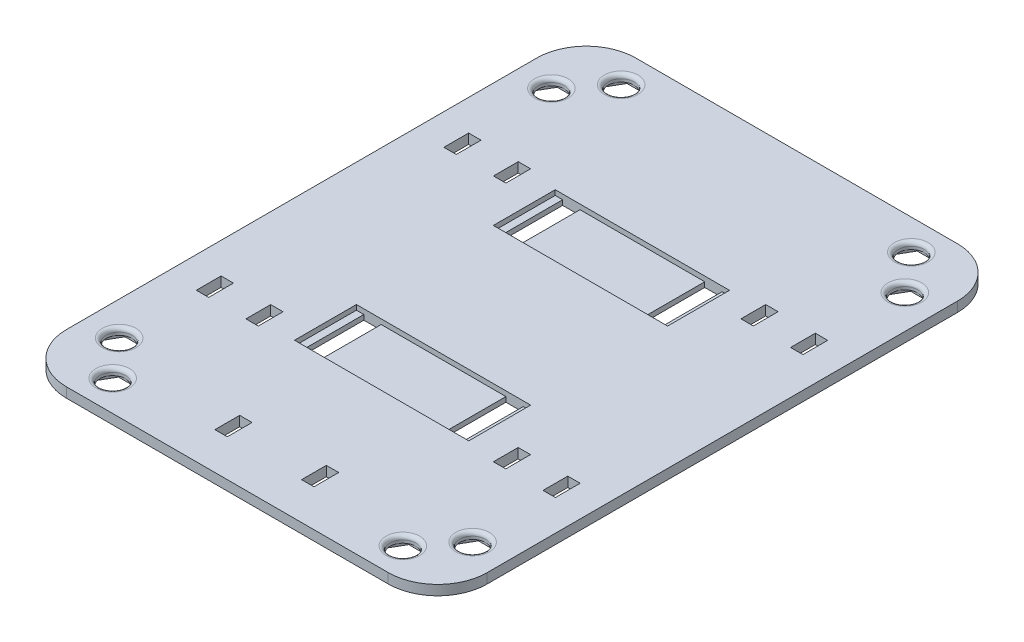
SolidWorks part; units mm, degrees
material "3-D Printed ABS"
ref_plane "Front Plane" through (0, 0, 0) normal (0, 0, 1) x (1, 0, 0)
ref_plane "Top Plane" through (0, 0, 0) normal (0, 1, 0) x (1, 0, 0)
ref_plane "Right Plane" through (0, 0, 0) normal (1, 0, 0) x (0, 0, -1)
sketch "Sketch1" plane through (0, 0, 0) normal (0, 1, 0) x (1, 0, 0)
  line L1 (-53.975, -73.025) -> (53.975, -73.025)
  line L2 (-53.975, -73.025) -> (-53.975, 73.025)
  line L3 (-53.975, 73.025) -> (53.975, 73.025)
  line L4 (53.975, -73.025) -> (53.975, 73.025)
  line L5 (-53.975, -73.025) -> (53.975, 73.025) construction
  line L6 (-53.975, 73.025) -> (53.975, -73.025) construction
  point P0 (0, 0)
  dimension "D1" = 107.95
  dimension "PlateY" = 146.05
extrude "Boss-Extrude1" add sketch "Sketch1" against normal blind 2.54
sketch "Sketch2" plane through (0, 0, 0) normal (0, 1, 0) x (1, 0, 0)
  line L0 (0, 0) -> (152.4, 0) construction
  line L1 (0, 0) -> (0, 152.4) construction
  line L4 (0, 0) -> (-53.975, 73.025) construction
  line L5 (0, 0) -> (-152.4, 0) construction
  line L6 (0, 0) -> (-152.4, 152.4) construction
  line L7 (-53.975, 73.025) -> (-53.975, -73.025) construction
  line L8 (53.975, 73.025) -> (-53.975, 73.025) construction
  line L9 (-152.4, 152.4) -> (-41.275, 60.325) construction
  line L10 (-41.275, 60.325) -> (0, 26.1257) construction
  line L11 (-30.7521, 73.025) -> (-53.975, 44.9974) construction
  circle A0 centre (-37.2189, 65.2108) radius 3.302
  circle A1 centre (45.3264, 55.4354) radius 3.302
  circle A2 centre (37.2189, 65.2108) radius 3.302
  circle A3 centre (-45.3264, -55.4354) radius 3.302
  circle A4 centre (-45.3264, 55.4354) radius 3.302
  circle A5 centre (-37.2189, -65.2108) radius 3.302
  circle A6 centre (37.2189, -65.2108) radius 3.302
  circle A7 centre (45.3264, -55.4354) radius 3.302
  point P12 (-41.275, 60.325)
  point P15 (-37.2189, 65.2108)
  dimension "D1" = 6.604
  dimension "D3" = 12.7
  dimension "D8" = 6.604
  dimension "D2" = 12.7
  dimension "D4" = 152.4
  dimension "D5" = 152.4
  dimension "D6" = 152.4
  dimension "D7" = 6.35
  dimension "D9" = 6.35
extrude "Cut-Extrude1" cut sketch "Sketch2" against normal through all
sketch "Sketch3" plane through (0, 0, 0) normal (0, 1, 0) x (1, 0, 0)
  line L0 (-53.975, 0) -> (53.975, 0) construction
  line L1 (-20.445, 33.4374) -> (-16, 33.4374)
  line L2 (-20.445, 33.4374) -> (-20.445, 17.5624)
  line L3 (-20.445, 17.5624) -> (-16, 17.5624)
  line L4 (-16, 33.4374) -> (-16, 17.5624)
  line L5 (16, 33.4374) -> (16, 17.5624)
  line L6 (20.445, 17.5624) -> (16, 17.5624)
  line L7 (20.445, 33.4374) -> (20.445, 17.5624)
  line L8 (20.445, 33.4374) -> (16, 33.4374)
  line L9 (-53.975, 73.025) -> (-53.975, -73.025) construction
  line L10 (53.975, -73.025) -> (53.975, 73.025) construction
  line L11 (0, -25.4999) -> (0, 79.6704) construction
  line L12 (0, 25.4999) -> (0, -79.6704) construction
  line L13 (20.445, -33.4374) -> (16, -33.4374)
  line L14 (20.445, -33.4374) -> (20.445, -17.5624)
  line L15 (20.445, -17.5624) -> (16, -17.5624)
  line L16 (16, -33.4374) -> (16, -17.5624)
  line L17 (-16, -33.4374) -> (-16, -17.5624)
  line L18 (-20.445, -17.5624) -> (-16, -17.5624)
  line L19 (-20.445, -33.4374) -> (-20.445, -17.5624)
  line L20 (-20.445, -33.4374) -> (-16, -33.4374)
  line L21 (-20.445, 25.4999) -> (-32.442, 25.4999) construction
  line L22 (-53.975, -73.025) -> (53.975, -73.025) construction
  point P31 (0, -73.025)
  point P32 (-53.975, 0)
  dimension "D1" = 15.875
  dimension "D2" = 4.445
  dimension "D3" = 16
  dimension "D4" = 25.4999
  dimension "D5" = 25.4999
extrude "Cut-Extrude2" cut sketch "Sketch3" against normal through all
fillet "Fillet1" radius 12.7 4 edges at (53.975, -1.27, -73.025) (53.975, -1.27, 73.025) (-53.975, -1.27, 73.025) (-53.975, -1.27, -73.025)
sketch "Sketch4" plane through (0, 0, 0) normal (0, 1, 0) x (1, 0, 0)
  line L0 (0, 0) -> (80.9727, -80.9727) construction
  line L1 (0, 0) -> (-80.9727, -80.9727) construction
  line L2 (69.1118, -51.1513) -> (28.7006, -10.7401)
  line L3 (28.7006, -10.7401) -> (10.7401, -28.7006)
  line L4 (10.7401, -28.7006) -> (51.1513, -69.1118)
  line L5 (51.1513, -69.1118) -> (69.1118, -51.1513)
  line L6 (0, 0) -> (0, -118.7381) construction
  line L7 (0, 0) -> (-98.4177, 0) construction
  line L8 (-51.1513, -69.1118) -> (-69.1118, -51.1513)
  line L9 (-69.1118, -51.1513) -> (-28.7006, -10.7401)
  line L10 (-28.7006, -10.7401) -> (-10.7401, -28.7006)
  line L11 (-10.7401, -28.7006) -> (-51.1513, -69.1118)
  line L12 (-69.1118, 51.1513) -> (-28.7006, 10.7401)
  line L13 (-51.1513, 69.1118) -> (-69.1118, 51.1513)
  line L14 (-10.7401, 28.7006) -> (-51.1513, 69.1118)
  line L15 (-28.7006, 10.7401) -> (-10.7401, 28.7006)
  line L16 (51.1513, 69.1118) -> (69.1118, 51.1513)
  line L17 (69.1118, 51.1513) -> (28.7006, 10.7401)
  line L18 (28.7006, 10.7401) -> (10.7401, 28.7006)
  line L19 (10.7401, 28.7006) -> (51.1513, 69.1118)
  point P6 (19.7204, -19.7204)
  dimension "D1" = 25.4
  dimension "D2" = 57.15
  dimension "D3" = 45
extrude "Cut-Extrude3" [suppressed] cut sketch "Sketch4" against normal blind 1.5875
sketch "Sketch6" [suppressed] plane through (0, 0, 0) normal (0, 1, 0) x (1, 0, 0)
  line L0 (46.3377, -44.1074) -> (34.6634, -32.4331) construction
  line L1 (0, 0) -> (0, -117.7376) construction
  line L2 (0, 0) -> (-151.7285, 0) construction
  line L4 (28.1601, -10.1996) -> (10.1996, -28.1601) construction
  line L5 (50.6107, -68.5712) -> (68.5712, -50.6107) construction
  text T0 "ESC" font "Century Gothic" height in points 22
  dimension "D1" = 45
  dimension "D2" = 20.32
  dimension "D3" = 20.32
extrude "Cut-Extrude5" [suppressed] cut sketch "Sketch6" against normal blind 3.175
sketch "Sketch5" plane through (0, 0, 0) normal (0, 1, 0) x (1, 0, 0)
  line L0 (41.275, 73.025) -> (-41.275, 73.025) construction
  line L1 (14.2875, 15.875) -> (-14.2875, 15.875)
  line L2 (14.2875, 15.875) -> (14.2875, 66.675)
  line L3 (14.2875, 66.675) -> (-14.2875, 66.675)
  line L4 (-14.2875, 15.875) -> (-14.2875, 66.675)
  point P4 (0, 15.875)
  dimension "D1" = 50.8
  dimension "D2" = 28.575
  dimension "D3" = 6.35
extrude "Cut-Extrude4" [suppressed] cut sketch "Sketch5" against normal blind 1.5875
ref_axis "Axis1" through (0, 0.3175, 0) along (0, -1, 0)
pattern_circular "CirPattern1" [suppressed] count 4 over 360 about axis through (0, 0.3175, 0) along (0, -1, 0) of bodies 105
sketch "Sketch7" plane through (0, 0, 0) normal (0, 1, 0) x (1, 0, 0)
  line L0 (0, 0) -> (0, -54.962) construction
  line L1 (63.4018, -13.3522) -> (38.0018, -13.3522)
  line L2 (63.4018, -13.3522) -> (63.4018, 43.7978)
  line L3 (63.4018, 43.7978) -> (38.0018, 43.7978)
  line L4 (38.0018, -13.3522) -> (38.0018, 43.7978)
  line L5 (-38.0018, -13.3522) -> (-38.0018, 43.7978)
  line L6 (-63.4018, 43.7978) -> (-38.0018, 43.7978)
  line L7 (-63.4018, -13.3522) -> (-63.4018, 43.7978)
  line L8 (-63.4018, -13.3522) -> (-38.0018, -13.3522)
  line L9 (-41.275, -73.025) -> (41.275, -73.025) construction
  line L10 (38.5677, -40.64) -> (-18.5823, -40.64)
  line L11 (38.5677, -40.64) -> (38.5677, -66.04)
  line L12 (38.5677, -66.04) -> (-18.5823, -66.04)
  line L13 (-18.5823, -40.64) -> (-18.5823, -66.04)
  line L14 (38.5677, -40.64) -> (-18.5823, -66.04) construction
  line L15 (38.5677, -66.04) -> (-18.5823, -40.64) construction
  line L16 (19.844, -36.1003) -> (-37.306, -36.1003)
  line L17 (19.844, -36.1003) -> (19.844, -61.5003)
  line L18 (19.844, -61.5003) -> (-37.306, -61.5003)
  line L19 (-37.306, -36.1003) -> (-37.306, -61.5003)
  line L20 (19.844, -36.1003) -> (-37.306, -61.5003) construction
  line L21 (19.844, -61.5003) -> (-37.306, -36.1003) construction
  point P11 (9.9927, -53.34)
  point P18 (-8.731, -48.8003)
  dimension "D1" = 57.15
  dimension "D2" = 25.4
  dimension "D3" = 57.15
  dimension "D4" = 25.4
  dimension "D5" = 6.985
  dimension "D6" = 57.15
  dimension "D7" = 25.4
extrude "Cut-Extrude6" [suppressed] cut sketch "Sketch7" against normal blind 1.27
sketch "Sketch8" plane through (0, 0, 0) normal (0, 1, 0) x (1, 0, 0)
  line L7 (19.05, -31.75) -> (-19.05, -31.75)
  line L8 (19.05, -31.75) -> (19.05, 31.75)
  line L9 (19.05, 31.75) -> (-19.05, 31.75)
  line L10 (-19.05, -31.75) -> (-19.05, 31.75)
  point P0 (0, 0)
  dimension "D1" = 38.1
  dimension "D2" = 31.75
  dimension "D3" = 63.5
extrude "Boss-Extrude3" [suppressed] add sketch "Sketch8" along normal blind 2.54
sketch "Sketch11" plane through (0, 0, 0) normal (0, 1, 0) x (1, 0, 0)
  line L0 (-20.445, -33.4374) -> (-16, -33.4374) construction
  line L1 (22.35, -33.4374) -> (-22.35, -33.4374)
  line L2 (22.35, -33.4374) -> (22.35, -17.5624)
  line L3 (22.35, -17.5624) -> (-22.35, -17.5624)
  line L4 (-22.35, -33.4374) -> (-22.35, -17.5624)
  line L5 (20.445, -17.5624) -> (16, -17.5624) construction
  line L6 (20.445, -33.4374) -> (20.445, -17.5624) construction
  line L7 (-20.445, -17.5624) -> (-20.445, -33.4374) construction
  line L8 (0, 0) -> (90.9737, 0) construction
  line L9 (-22.35, 33.4374) -> (-22.35, 17.5624)
  line L10 (22.35, 17.5624) -> (-22.35, 17.5624)
  line L11 (22.35, 33.4374) -> (22.35, 17.5624)
  line L12 (22.35, 33.4374) -> (-22.35, 33.4374)
  dimension "D1" = 1.905
  dimension "D2" = 1.905
extrude "Cut-Extrude9" cut sketch "Sketch11" against normal mid plane 2.54
sketch "Sketch12" plane through (0, 0, 0) normal (0, 1, 0) x (1, 0, 0)
  line L1 (12.7, -41.6354) -> (-12.7, -41.6354)
  line L2 (12.7, -41.6354) -> (12.7, -25.4999)
  line L3 (12.7, -25.4999) -> (-12.7, -25.4999)
  line L4 (-12.7, -41.6354) -> (-12.7, -25.4999)
  line L6 (23.8125, 0) -> (-23.8125, 0) construction
  line L7 (-53.975, 60.325) -> (-53.975, -60.325) construction
  line L9 (-12.7, 41.6354) -> (-12.7, 25.4999)
  line L10 (12.7, 25.4999) -> (-12.7, 25.4999)
  line L11 (12.7, 41.6354) -> (12.7, 25.4999)
  line L12 (12.7, 41.6354) -> (-12.7, 41.6354)
  point P6 (-53.975, 0)
  dimension "D1" = 25.4
  dimension "D2" = 25.4999
extrude "Cut-Extrude12" [suppressed] cut sketch "Sketch12" along normal through all
sketch "Sketch9" plane through (0, 0, 0) normal (0, 1, 0) x (1, 0, 0)
  line L1 (25.1579, -52.4084) -> (-25.6421, -52.4084)
  line L2 (25.1579, -52.4084) -> (25.1579, -1.6084)
  line L3 (25.1579, -1.6084) -> (-25.6421, -1.6084)
  line L4 (-25.6421, -52.4084) -> (-25.6421, -1.6084)
  line L5 (25.1579, -52.4084) -> (-25.6421, -1.6084) construction
  line L6 (25.1579, -1.6084) -> (-25.6421, -52.4084) construction
  point P0 (-0.2421, -27.0084)
  dimension "D1" = 50.8
  dimension "D2" = 50.8
sketch "Sketch13" plane through (0, 0, 0) normal (0, 1, 0) x (1, 0, 0)
  line L0 (0, 0) -> (0, -106.7514) construction
  line L1 (34.925, 3.175) -> (28.575, 3.175)
  line L2 (34.925, 3.175) -> (34.925, -3.175)
  line L3 (34.925, -3.175) -> (28.575, -3.175)
  line L4 (28.575, 3.175) -> (28.575, -3.175)
  line L5 (34.925, 3.175) -> (28.575, -3.175) construction
  line L6 (34.925, -3.175) -> (28.575, 3.175) construction
  line L7 (-34.925, -3.175) -> (-28.575, 3.175) construction
  line L8 (-34.925, 3.175) -> (-28.575, -3.175) construction
  line L9 (-28.575, 3.175) -> (-28.575, -3.175)
  line L10 (-34.925, -3.175) -> (-28.575, -3.175)
  line L11 (-34.925, 3.175) -> (-34.925, -3.175)
  line L12 (-34.925, 3.175) -> (-28.575, 3.175)
  point P0 (31.75, 0)
  point P12 (-31.75, 0)
  dimension "D1" = 6.35
  dimension "D2" = 28.575
  dimension "D3" = 0
extrude "Cut-Extrude13" [suppressed] cut sketch "Sketch13" against normal through all
fillet "Fillet2" radius 1.016 8 edges at (-37.2189, 0, -61.9088) (37.2189, 0, 68.5128) (45.3264, 0, 58.7374) (-37.2189, 0, 61.9088) (-45.3264, 0, 52.1334) (45.3264, 0, -58.7374) (37.2189, 0, -68.5128) (-45.3264, 0, -52.1334)
sketch "Sketch14" plane through (0, 0, 0) normal (0, 1, 0) x (1, 0, 0)
  line L0 (0, 76.698) -> (0, -76.698) construction
  line L1 (33.3248, -34.925) -> (30.1498, -34.925)
  line L2 (33.3248, -34.925) -> (33.3248, -28.575)
  line L3 (33.3248, -28.575) -> (30.1498, -28.575)
  line L4 (30.1498, -34.925) -> (30.1498, -28.575)
  line L5 (0, 0) -> (-92.4571, 0) construction
  line L6 (-30.1498, -34.925) -> (-30.1498, -28.575)
  line L7 (-33.3248, -28.575) -> (-30.1498, -28.575)
  line L8 (-33.3248, -34.925) -> (-33.3248, -28.575)
  line L9 (-33.3248, -34.925) -> (-30.1498, -34.925)
  line L10 (-33.3248, 34.925) -> (-30.1498, 34.925)
  line L11 (-33.3248, 34.925) -> (-33.3248, 28.575)
  line L12 (-33.3248, 28.575) -> (-30.1498, 28.575)
  line L13 (-30.1498, 34.925) -> (-30.1498, 28.575)
  line L14 (30.1498, 34.925) -> (30.1498, 28.575)
  line L15 (33.3248, 28.575) -> (30.1498, 28.575)
  line L16 (33.3248, 34.925) -> (33.3248, 28.575)
  line L17 (33.3248, 34.925) -> (30.1498, 34.925)
  line L18 (-41.275, -73.025) -> (41.275, -73.025) construction
  line L19 (-9.525, -63.5) -> (-9.525, -57.15)
  line L20 (12.7, -63.5) -> (9.525, -63.5)
  line L21 (12.7, -63.5) -> (12.7, -57.15)
  line L22 (12.7, -57.15) -> (9.525, -57.15)
  line L23 (38.1, -73.025) -> (38.1, 73.025) construction
  line L24 (41.275, 73.025) -> (-41.275, 73.025) construction
  line L25 (42.8752, 34.925) -> (46.0502, 34.925)
  line L26 (42.8752, 34.925) -> (42.8752, 28.575)
  line L27 (42.8752, 28.575) -> (46.0502, 28.575)
  line L28 (46.0502, 34.925) -> (46.0502, 28.575)
  line L29 (46.0502, -34.925) -> (46.0502, -28.575)
  line L30 (42.8752, -28.575) -> (46.0502, -28.575)
  line L31 (42.8752, -34.925) -> (42.8752, -28.575)
  line L32 (42.8752, -34.925) -> (46.0502, -34.925)
  line L33 (-46.0502, 34.925) -> (-46.0502, 28.575)
  line L34 (-42.8752, 28.575) -> (-46.0502, 28.575)
  line L35 (-42.8752, 34.925) -> (-42.8752, 28.575)
  line L36 (-42.8752, 34.925) -> (-46.0502, 34.925)
  line L37 (-42.8752, -34.925) -> (-46.0502, -34.925)
  line L38 (-42.8752, -34.925) -> (-42.8752, -28.575)
  line L39 (-42.8752, -28.575) -> (-46.0502, -28.575)
  line L40 (-46.0502, -34.925) -> (-46.0502, -28.575)
  line L41 (53.975, -50.8) -> (-53.975, -50.8) construction
  line L42 (53.975, -60.325) -> (53.975, 60.325) construction
  line L43 (-53.975, 60.325) -> (-53.975, -60.325) construction
  line L44 (0, -178.298) -> (0, -24.902) construction
  line L45 (9.525, -63.5) -> (9.525, -57.15)
  line L46 (-12.7, -57.15) -> (-9.525, -57.15)
  line L47 (-12.7, -63.5) -> (-12.7, -57.15)
  line L48 (-12.7, -63.5) -> (-9.525, -63.5)
  dimension "D2" = 3.175
  dimension "D3" = 6.35
  dimension "D4" = 28.575
  dimension "D5" = 3.175
  dimension "D6" = 6.35
  dimension "D7" = 9.525
  dimension "D8" = 9.525
  dimension "D9" = 38.1
  dimension "D10" = 22.225
  dimension "D11" = 30.1498
extrude "Cut-Extrude14" cut sketch "Sketch14" against normal through all
sketch "Sketch17" plane through (0, -2.54, 0) normal (0, -1, 0) x (1, 0, 0)
  line L0 (0, 0) -> (-152.4, 0) construction
  line L1 (0, 0) -> (0, -152.4) construction
  line L2 (0, -152.4) -> (-152.4, -152.4) construction
  line L3 (-152.4, -152.4) -> (-152.4, 0) construction
  line L4 (-152.4, -152.4) -> (0, 0) construction
  line L5 (41.275, -73.025) -> (-41.275, -73.025) construction
  line L6 (-53.975, -60.325) -> (-53.975, 60.325) construction
  line L7 (-152.4, -152.4) -> (-41.275, -60.325) construction
  line L8 (-41.275, -60.325) -> (0, -26.1257) construction
  line L9 (43.2734, -51.8794) -> (47.3795, -51.8794)
  line L10 (-41.2203, -55.4354) -> (-43.2734, -51.8794)
  line L11 (-43.2734, -51.8794) -> (-47.3795, -51.8794)
  line L12 (-47.3795, -51.8794) -> (-49.4325, -55.4354)
  line L13 (-49.4325, -55.4354) -> (-47.3795, -58.9914)
  line L14 (-47.3795, -58.9914) -> (-43.2734, -58.9914)
  line L15 (-43.2734, -58.9914) -> (-41.2203, -55.4354)
  line L16 (-33.1128, -65.2108) -> (-35.1659, -61.6548)
  line L17 (-35.1659, -61.6548) -> (-39.272, -61.6548)
  line L18 (-39.272, -61.6548) -> (-41.3251, -65.2108)
  line L19 (-41.3251, -65.2108) -> (-39.272, -68.7668)
  line L20 (-39.272, -68.7668) -> (-35.1659, -68.7668)
  line L21 (-35.1659, -68.7668) -> (-33.1128, -65.2108)
  line L22 (47.3795, -51.8794) -> (49.4325, -55.4354)
  line L23 (49.4325, -55.4354) -> (47.3795, -58.9914)
  line L24 (41.2203, -55.4354) -> (43.2734, -51.8794)
  line L25 (43.2734, -58.9914) -> (41.2203, -55.4354)
  line L26 (47.3795, -58.9914) -> (43.2734, -58.9914)
  line L27 (35.1659, -61.6548) -> (39.272, -61.6548)
  line L28 (33.1128, -65.2108) -> (35.1659, -61.6548)
  line L29 (39.272, -61.6548) -> (41.3251, -65.2108)
  line L30 (41.3251, -65.2108) -> (39.272, -68.7668)
  line L31 (35.1659, -68.7668) -> (33.1128, -65.2108)
  line L32 (39.272, -68.7668) -> (35.1659, -68.7668)
  line L33 (-41.2203, 55.4354) -> (-43.2734, 51.8794)
  line L34 (-43.2734, 51.8794) -> (-47.3795, 51.8794)
  line L35 (-47.3795, 51.8794) -> (-49.4325, 55.4354)
  line L36 (-49.4325, 55.4354) -> (-47.3795, 58.9914)
  line L37 (-47.3795, 58.9914) -> (-43.2734, 58.9914)
  line L38 (-43.2734, 58.9914) -> (-41.2203, 55.4354)
  line L39 (-33.1128, 65.2108) -> (-35.1659, 61.6548)
  line L40 (-35.1659, 61.6548) -> (-39.272, 61.6548)
  line L41 (-39.272, 61.6548) -> (-41.3251, 65.2108)
  line L42 (-41.3251, 65.2108) -> (-39.272, 68.7668)
  line L43 (-39.272, 68.7668) -> (-35.1659, 68.7668)
  line L44 (-35.1659, 68.7668) -> (-33.1128, 65.2108)
  line L45 (39.272, 68.7668) -> (35.1659, 68.7668)
  line L46 (35.1659, 68.7668) -> (33.1128, 65.2108)
  line L47 (41.3251, 65.2108) -> (39.272, 68.7668)
  line L48 (39.272, 61.6548) -> (41.3251, 65.2108)
  line L49 (33.1128, 65.2108) -> (35.1659, 61.6548)
  line L50 (35.1659, 61.6548) -> (39.272, 61.6548)
  line L51 (47.3795, 58.9914) -> (43.2734, 58.9914)
  line L52 (43.2734, 58.9914) -> (41.2203, 55.4354)
  line L53 (41.2203, 55.4354) -> (43.2734, 51.8794)
  line L54 (49.4325, 55.4354) -> (47.3795, 58.9914)
  line L55 (47.3795, 51.8794) -> (49.4325, 55.4354)
  line L56 (43.2734, 51.8794) -> (47.3795, 51.8794)
  circle A0 centre (-45.3264, -55.4354) radius 3.556 construction
  circle A1 centre (-37.2189, -65.2108) radius 3.556 construction
  point P0 (0, 0)
  point P6 (-41.275, -60.2488)
  dimension "D1" = 12.7762
  dimension "D2" = 12.7
  dimension "D3" = 7.112
  dimension "D4" = 7.112
extrude "Cut-Extrude15" cut sketch "Sketch17" against normal blind 0.7937
equation "\"Plate Dim Y\"= \"Plate Dim Y@Quad Assemb.SLDASM\""
equation "\"PlateY@Sketch1\" = \"Plate Dim Y\""
equation "\"D1@Sketch1\"= \"Plate Dim X\""
equation "\"D1@Boss-Extrude1\" = \"Plate Thickness\""
equation "\"Plate Dim X\"= \"Plate Dim X@Quad Assemb.SLDASM\""
equation "\"Plate Thickness\"= \"Plate Thickness@Quad Assemb.sldasm\""
equation "\"Batt X\"= \"Batt X@Quad Assemb.sldasm\""
equation "\"Batt Y\"= \"Batt Y@Quad Assemb.sldasm\""
equation "\"D3@Sketch3\"=\"Batt X\"/2"
equation "\"D4@Sketch3\"=\"Batt Y\"/4"
equation "\"D5@Sketch3\"=\"Batt Y\"*2/8"
equation "\"Dowell Width\"= \"Dowell Width@Quad Assemb.sldasm\""
equation "\"D1@Sketch2\"=\"Dowell Width\"+.01"
equation "\"D2@Sketch12\"=\"Batt Y\"/4"
equation "\"D7@Sketch2\"=\"Dowell Width\""
equation "\"D8@Sketch2\"=\"Dowell Width\" +0.01in"
equation "\"D9@Sketch2\"=\"Dowell Width\""
